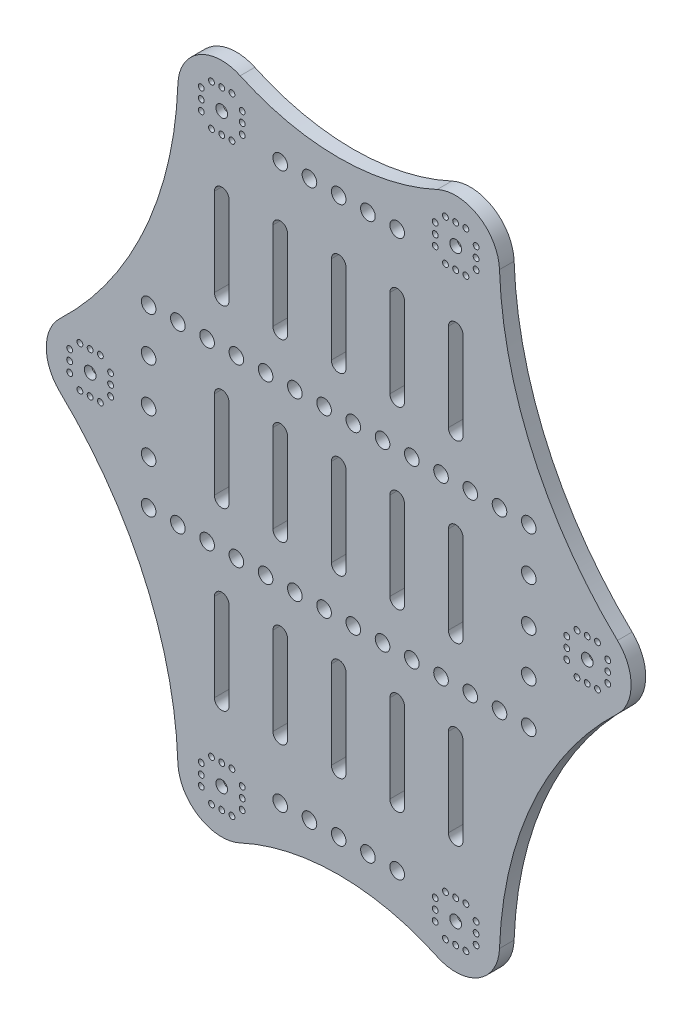
SolidWorks part; units mm, degrees
ref_plane "前视基准面" through (0, 0, 0) normal (0, 0, 1) x (1, 0, 0)
ref_plane "上视基准面" through (0, 0, 0) normal (0, 1, 0) x (1, 0, 0)
ref_plane "右视基准面" through (0, 0, 0) normal (1, 0, 0) x (0, 0, -1)
other "Configuration Table"
sketch "Sketch1" plane through (0, 0, 0) normal (0, 0, 1) x (1, 0, 0)
  line L0 (0, 0) -> (0, 100) construction
  line L1 (0, 100) -> (40, 100) construction
  line L2 (0, 0) -> (85, 0) construction
  circle A1 centre (85, 0) radius 15
  circle A2 centre (40, 100) radius 15
  circle A3 centre (-85, 0) radius 15
  circle A4 centre (-40, 100) radius 15
  circle A5 centre (40, -100) radius 15
  circle A6 centre (-40, -100) radius 15
  arc A7 (-33.6842, 113.6055) -> (33.6842, 113.6055) centre (0, 186.1684) ccw
  arc A8 (-33.6842, -113.6055) -> (33.6842, -113.6055) centre (0, -186.1684) cw
  arc A9 (-95.3356, 10.8708) -> (-54.9908, 100.526) centre (-184.9108, 105.0849) ccw
  arc A10 (95.3356, 10.8708) -> (54.9908, 100.526) centre (184.9108, 105.0849) cw
  arc A11 (95.3356, -10.8708) -> (54.9908, -100.526) centre (184.9108, -105.0849) ccw
  arc A12 (-95.3356, -10.8708) -> (-54.9908, -100.526) centre (-184.9108, -105.0849) cw
  dimension "D1" = 30
  dimension "D2" = 30
  dimension "D6" = 80
  dimension "D7" = 130
  dimension "D3" = 40
  dimension "D4" = 85
  dimension "D5" = 100
extrude "Boss-Extrude1" add sketch "Sketch1" along normal blind 5 contours A3 A12 A6 A8 A5 A11 A1 A10 A2 A7 A4 A9 | A3 | A4 | A2 | A1 | A5 | A6 A7 region at (85, 0, 0) region at (0, 0, 0) region at (40, 100, 0) region at (40, -100, 0) region at (-40, 100, 0) region at (-40, -100, 0) region at (-85, 0, 0)
sketch "Sketch2" plane through (0, 0, 0) normal (0, 0, -1) x (-1, 0, 0)
  line L0 (0, 0) -> (0, 91.5521) construction
  line L1 (0, 0) -> (39.9574, 0) construction
  circle A0 centre (-40, 100) radius 11.25
  circle A1 centre (-85, 0) radius 11.25
  circle A2 centre (85, 0) radius 11.25
  circle A3 centre (40, 100) radius 11.25
  circle A4 centre (40, -100) radius 11.25
  circle A5 centre (-40, -100) radius 11.25
  dimension "D1" = 22.5
extrude "Cut-Extrude1" cut sketch "Sketch2" against normal blind 2.5
sketch "Sketch3" plane through (0, 0, 2.5) normal (0, 0, -1) x (-1, 0, 0)
  line L0 (-40, 100) -> (-40, 107) construction
  line L1 (-40, 107) -> (-36.5, 107) construction
  line L2 (-85, 0) -> (-85, 7) construction
  line L3 (-85, 7) -> (-81.5, 7) construction
  circle A0 centre (-40, 100) radius 2
  circle A1 centre (-40, 107) radius 1
  circle A2 centre (-36.5, 107) radius 1
  circle A3 centre (-43.5, 107) radius 1
  circle A4 centre (-40, 100) radius 2
  circle A5 centre (-33, 103.5) radius 1
  circle A6 centre (-33, 100) radius 1
  circle A7 centre (-33, 96.5) radius 1
  circle A8 centre (-40, 100) radius 2
  circle A9 centre (-36.5, 93) radius 1
  circle A10 centre (-40, 93) radius 1
  circle A11 centre (-43.5, 93) radius 1
  circle A12 centre (-40, 100) radius 2
  circle A13 centre (-47, 96.5) radius 1
  circle A14 centre (-47, 100) radius 1
  circle A15 centre (-47, 103.5) radius 1
  circle A16 centre (-85, 0) radius 2
  circle A17 centre (-85, 7) radius 1
  circle A18 centre (-81.5, 7) radius 1
  circle A19 centre (-88.5, 7) radius 1
  circle A41 centre (-85, 0) radius 2
  circle A42 centre (-78, 3.5) radius 1
  circle A43 centre (-78, 0) radius 1
  circle A44 centre (-78, -3.5) radius 1
  circle A45 centre (-85, 0) radius 2
  circle A46 centre (-81.5, -7) radius 1
  circle A47 centre (-85, -7) radius 1
  circle A48 centre (-88.5, -7) radius 1
  circle A49 centre (-85, 0) radius 2
  circle A50 centre (-92, -3.5) radius 1
  circle A51 centre (-92, 0) radius 1
  circle A52 centre (-92, 3.5) radius 1
  point P33 (-40, 100)
  point P63 (-85, 0)
  dimension "D1" = 4
  dimension "D2" = 2
  dimension "D4" = 2
  dimension "D7" = 4
  dimension "D8" = 2
  dimension "D10" = 2
  dimension "D3" = 7
  dimension "D5" = 3.5
  dimension "D9" = 7
  dimension "D11" = 3.5
  dimension "D12" = 4
  dimension "D6" = 4
extrude "Cut-Extrude2" cut sketch "Sketch3" against normal blind 2.5 contours A15 | A14 | A13 | A0 | A11 | A10 | A9 | A7 | A6 | A5 | A2 | A1 | A3 | A47 | A49 | A43 | A45 | A16 | A50 | A51 | A52 | A19 | A17 | A18 | A46 | A48 | A44 | A42
mirror "Mirror1" about plane through (0, 0, 0) normal (1, 0, 0) of "Cut-Extrude2"
mirror "Mirror2" about plane through (0, 0, 0) normal (0, 1, 0) of "Cut-Extrude2", "Mirror1"
sketch "Sketch4" plane through (0, 0, 5) normal (0, 0, 1) x (1, 0, 0)
  arc A24 (-70.9715, 0) -> (-31.105, 85.8815) centre (-184.9108, 105.0849) ccw
  arc A25 (-31.105, -85.8815) -> (-70.9715, 0) centre (-184.9108, -105.0849) ccw
  arc A26 (31.105, -85.8815) -> (-31.105, -85.8815) centre (0, -186.1684) ccw
  arc A27 (70.9715, 0) -> (31.105, -85.8815) centre (184.9108, -105.0849) ccw
  arc A28 (31.105, 85.8815) -> (70.9715, 0) centre (184.9108, 105.0849) ccw
  arc A29 (-31.105, 85.8815) -> (31.105, 85.8815) centre (0, 186.1684) ccw
  arc A30 (-70.9715, 0) -> (-31.105, 85.8815) centre (-184.9108, 105.0849) ccw
  arc A31 (-31.105, -85.8815) -> (-70.9715, 0) centre (-184.9108, -105.0849) ccw
  arc A32 (31.105, -85.8815) -> (-31.105, -85.8815) centre (0, -186.1684) ccw
  arc A33 (70.9715, 0) -> (31.105, -85.8815) centre (184.9108, -105.0849) ccw
  arc A34 (31.105, 85.8815) -> (70.9715, 0) centre (184.9108, 105.0849) ccw
  arc A35 (-31.105, 85.8815) -> (31.105, 85.8815) centre (0, 186.1684) ccw
  dimension "D1" = 25
extrude "Cut-Extrude3" [suppressed] cut sketch "Sketch4" against normal through all
fillet "Fillet1" [suppressed] radius 20
sketch "Sketch5" plane through (0, 0, 0) normal (0, 0, -1) x (-1, 0, 0)
  line L0 (0, 95) -> (0, 106.1684) construction
  line L1 (0, 95) -> (20, 95) construction
  line L2 (0, -95) -> (0, -106.1684) construction
  line L3 (0, 0) -> (50.0339, 0) construction
  line L5 (0, -95) -> (20, -95) construction
  circle A0 centre (20, 95) radius 2.5
  circle A1 centre (0, 95) radius 2.5
  circle A2 centre (10, 95) radius 2.5
  circle A17 centre (10, -95) radius 2.5
  circle A18 centre (0, -95) radius 2.5
  circle A19 centre (20, -95) radius 2.5
  arc A20 (-33.6842, 113.6055) -> (33.6842, 113.6055) centre (0, 186.1684) ccw construction
  circle A21 centre (-20, 95) radius 2.5
  circle A22 centre (-10, 95) radius 2.5
  arc A23 (33.6842, -113.6055) -> (-33.6842, -113.6055) centre (0, -186.1684) ccw construction
  circle A24 centre (-20, -95) radius 2.5
  circle A25 centre (-10, -95) radius 2.5
  dimension "D1" = 5
  dimension "D2" = 5
  dimension "D4" = 5
  dimension "D3" = 95
  dimension "D5" = 10
extrude "Cut-Extrude4" cut sketch "Sketch5" against normal blind 12.5
sketch "Sketch7" [suppressed] plane through (0, 0, 0) normal (0, 0, -1) x (-1, 0, 0)
  line L0 (-142.3284, 63.1511) -> (-138.4501, 72.3684) construction
  line L1 (-66.361, 51.7375) -> (-44.32, 39.8221) construction
  line L2 (-152.9421, 69.9963) -> (-131.7148, 56.3059) construction
  line L3 (-131.7148, 56.3059) -> (-142.3284, 63.1511) construction
  line L4 (-55.3405, 45.7798) -> (-52.1848, 55.2688) construction
  circle A6 centre (-142.3284, 63.1511) radius 2.5
  circle A7 centre (-138.4501, 72.3684) radius 2.5
  circle A8 centre (-134.5717, 81.5857) radius 2.5
  circle A9 centre (-142.3284, 63.1511) radius 2.5
  circle A10 centre (-146.2068, 53.9338) radius 2.5
  circle A11 centre (-150.0851, 44.7165) radius 2.5
  arc A12 (-95.3356, 10.8708) -> (-54.9908, 100.526) centre (-184.9108, 105.0849) ccw construction
  arc A13 (-70.9715, 0) -> (-31.105, 85.8815) centre (-184.9108, 105.0849) ccw construction
  circle A14 centre (-55.3405, 45.7798) radius 2.5
  circle A15 centre (-52.1848, 55.2688) radius 2.5
  circle A16 centre (-48.3064, 64.4861) radius 2.5
  circle A17 centre (-59.2189, 36.5625) radius 2.5
  circle A18 centre (-63.0972, 27.3452) radius 2.5
  dimension "D1" = 5
  dimension "D2" = 5
  dimension "D7" = 5
  dimension "D9" = 5
  dimension "D3" = 100
  dimension "D4" = 10
  dimension "D5" = 10
  dimension "D6" = 10
  dimension "D8" = 100
  dimension "D10" = 10
  dimension "D11" = 2
extrude "Cut-Extrude5" [suppressed] cut sketch "Sketch7" against normal blind 10 contours A14 | A17 | A18 | A16 | A15
sketch "Sketch8" plane through (0, 0, 5) normal (0, 0, 1) x (1, 0, 0)
  line L0 (0, 0) -> (0, 75) construction
  line L1 (0, 75) -> (40, 75) construction
  line L2 (40, 75) -> (40, 45) construction
  line L3 (42.5, 75) -> (42.5, 45)
  line L4 (37.5, 75) -> (37.5, 45)
  line L5 (20, 75) -> (20, 45) construction
  line L6 (22.5, 75) -> (22.5, 45)
  line L7 (17.5, 75) -> (17.5, 45)
  line L8 (0, 75) -> (0, 45) construction
  line L9 (2.5, 75) -> (2.5, 45)
  line L10 (-2.5, 75) -> (-2.5, 45)
  line L11 (-20, 75) -> (-20, 45) construction
  line L12 (-17.5, 75) -> (-17.5, 45)
  line L13 (-22.5, 75) -> (-22.5, 45)
  line L14 (-40, 75) -> (-40, 45) construction
  line L15 (-37.5, 75) -> (-37.5, 45)
  line L16 (-42.5, 75) -> (-42.5, 45)
  line L17 (40, 100) -> (0, 100) construction
  line L18 (0, 15) -> (40, 15) construction
  line L19 (40, 15) -> (40, -15) construction
  line L20 (42.5, 15) -> (42.5, -15)
  line L21 (37.5, 15) -> (37.5, -15)
  line L22 (20, 15) -> (20, -15) construction
  line L23 (22.5, 15) -> (22.5, -15)
  line L24 (17.5, 15) -> (17.5, -15)
  line L25 (0, 15) -> (0, -15) construction
  line L26 (2.5, 15) -> (2.5, -15)
  line L27 (-2.5, 15) -> (-2.5, -15)
  line L28 (-20, 15) -> (-20, -15) construction
  line L29 (-17.5, 15) -> (-17.5, -15)
  line L30 (-22.5, 15) -> (-22.5, -15)
  line L31 (-40, 15) -> (-40, -15) construction
  line L32 (-37.5, 15) -> (-37.5, -15)
  line L33 (-42.5, 15) -> (-42.5, -15)
  line L34 (0, -45) -> (40, -45) construction
  line L35 (40, -45) -> (40, -75) construction
  line L36 (42.5, -45) -> (42.5, -75)
  line L37 (37.5, -45) -> (37.5, -75)
  line L38 (20, -45) -> (20, -75) construction
  line L39 (22.5, -45) -> (22.5, -75)
  line L40 (17.5, -45) -> (17.5, -75)
  line L41 (0, -45) -> (0, -75) construction
  line L42 (2.5, -45) -> (2.5, -75)
  line L43 (-2.5, -45) -> (-2.5, -75)
  line L44 (-20, -45) -> (-20, -75) construction
  line L45 (-17.5, -45) -> (-17.5, -75)
  line L46 (-22.5, -45) -> (-22.5, -75)
  line L47 (-40, -45) -> (-40, -75) construction
  line L48 (-37.5, -45) -> (-37.5, -75)
  line L49 (-42.5, -45) -> (-42.5, -75)
  arc A0 (42.5, 75) -> (37.5, 75) centre (40, 75) ccw
  arc A1 (37.5, 45) -> (42.5, 45) centre (40, 45) ccw
  arc A2 (22.5, 75) -> (17.5, 75) centre (20, 75) ccw
  arc A3 (17.5, 45) -> (22.5, 45) centre (20, 45) ccw
  arc A4 (2.5, 75) -> (-2.5, 75) centre (0, 75) ccw
  arc A5 (-2.5, 45) -> (2.5, 45) centre (0, 45) ccw
  arc A6 (-17.5, 75) -> (-22.5, 75) centre (-20, 75) ccw
  arc A7 (-22.5, 45) -> (-17.5, 45) centre (-20, 45) ccw
  arc A8 (-37.5, 75) -> (-42.5, 75) centre (-40, 75) ccw
  arc A9 (-42.5, 45) -> (-37.5, 45) centre (-40, 45) ccw
  arc A10 (42.5, 15) -> (37.5, 15) centre (40, 15) ccw
  arc A11 (37.5, -15) -> (42.5, -15) centre (40, -15) ccw
  arc A12 (22.5, 15) -> (17.5, 15) centre (20, 15) ccw
  arc A13 (17.5, -15) -> (22.5, -15) centre (20, -15) ccw
  arc A14 (2.5, 15) -> (-2.5, 15) centre (0, 15) ccw
  arc A15 (-2.5, -15) -> (2.5, -15) centre (0, -15) ccw
  arc A16 (-17.5, 15) -> (-22.5, 15) centre (-20, 15) ccw
  arc A17 (-22.5, -15) -> (-17.5, -15) centre (-20, -15) ccw
  arc A18 (-37.5, 15) -> (-42.5, 15) centre (-40, 15) ccw
  arc A19 (-42.5, -15) -> (-37.5, -15) centre (-40, -15) ccw
  arc A20 (42.5, -45) -> (37.5, -45) centre (40, -45) ccw
  arc A21 (37.5, -75) -> (42.5, -75) centre (40, -75) ccw
  arc A22 (22.5, -45) -> (17.5, -45) centre (20, -45) ccw
  arc A23 (17.5, -75) -> (22.5, -75) centre (20, -75) ccw
  arc A24 (2.5, -45) -> (-2.5, -45) centre (0, -45) ccw
  arc A25 (-2.5, -75) -> (2.5, -75) centre (0, -75) ccw
  arc A26 (-17.5, -45) -> (-22.5, -45) centre (-20, -45) ccw
  arc A27 (-22.5, -75) -> (-17.5, -75) centre (-20, -75) ccw
  arc A28 (-37.5, -45) -> (-42.5, -45) centre (-40, -45) ccw
  arc A29 (-42.5, -75) -> (-37.5, -75) centre (-40, -75) ccw
  point P3 (40, 60)
  point P11 (20, 60)
  point P18 (0, 60)
  point P25 (-20, 60)
  point P32 (-40, 60)
  point P44 (40, 0)
  point P51 (20, 0)
  point P58 (0, 0)
  point P65 (-20, 0)
  point P72 (-40, 0)
  point P80 (40, -60)
  point P87 (20, -60)
  point P94 (0, -60)
  point P101 (-20, -60)
  point P108 (-40, -60)
  dimension "D3" = 2.5
  dimension "D1" = 40
  dimension "D2" = 75
  dimension "D4" = 30
  dimension "D6" = 20
  dimension "D8" = 60
  dimension "D5" = 5
  dimension "D7" = 3
extrude "Cut-Extrude6" cut sketch "Sketch8" against normal blind 10
sketch "Sketch9" plane through (0, 0, 5) normal (0, 0, 1) x (1, 0, 0)
  line L0 (0, 0) -> (0, 30) construction
  line L1 (0, 30) -> (-65, 30) construction
  line L2 (0, 0) -> (85, 0) construction
  line L3 (0, -30) -> (-65, -30) construction
  circle A0 centre (-65, 30) radius 2.5
  circle A1 centre (-55, 30) radius 2.5
  circle A2 centre (-45, 30) radius 2.5
  circle A3 centre (-35, 30) radius 2.5
  circle A4 centre (-25, 30) radius 2.5
  circle A5 centre (-15, 30) radius 2.5
  circle A6 centre (-5, 30) radius 2.5
  circle A7 centre (5, 30) radius 2.5
  circle A8 centre (15, 30) radius 2.5
  circle A9 centre (25, 30) radius 2.5
  circle A10 centre (35, 30) radius 2.5
  circle A11 centre (45, 30) radius 2.5
  circle A12 centre (55, 30) radius 2.5
  circle A13 centre (65, 30) radius 2.5
  circle A14 centre (65, -30) radius 2.5
  circle A15 centre (55, -30) radius 2.5
  circle A16 centre (45, -30) radius 2.5
  circle A17 centre (35, -30) radius 2.5
  circle A18 centre (25, -30) radius 2.5
  circle A19 centre (15, -30) radius 2.5
  circle A20 centre (5, -30) radius 2.5
  circle A21 centre (-5, -30) radius 2.5
  circle A22 centre (-15, -30) radius 2.5
  circle A23 centre (-25, -30) radius 2.5
  circle A24 centre (-35, -30) radius 2.5
  circle A25 centre (-45, -30) radius 2.5
  circle A26 centre (-55, -30) radius 2.5
  circle A27 centre (-65, -30) radius 2.5
  dimension "D1" = 5
  dimension "D2" = 30
  dimension "D3" = 65
  dimension "D5" = 10
  dimension "D4" = 14
extrude "Cut-Extrude7" cut sketch "Sketch9" against normal blind 10
sketch "Sketch10" plane through (0, 0, 5) normal (0, 0, 1) x (1, 0, 0)
  line L0 (0, 0) -> (-65, 0) construction
  line L1 (-65, 0) -> (-40, 15) construction
  line L2 (-40, 15) -> (-65, 15) construction
  line L3 (-65, 15) -> (-65, 0) construction
  line L4 (0, 0) -> (0, 17.5) construction
  circle A1 centre (-65, 0) radius 2.5
  circle A2 centre (-65, 15) radius 2.5
  circle A3 centre (-65, -15) radius 2.5
  arc A4 (2.5, 15) -> (-2.5, 15) centre (0, 15) ccw construction
  circle A5 centre (65, -15) radius 2.5
  circle A6 centre (65, 0) radius 2.5
  circle A7 centre (65, 15) radius 2.5
  dimension "D1" = 5
  dimension "D3" = 5
  dimension "D2" = 65
extrude "Cut-Extrude8" cut sketch "Sketch10" against normal blind 10
